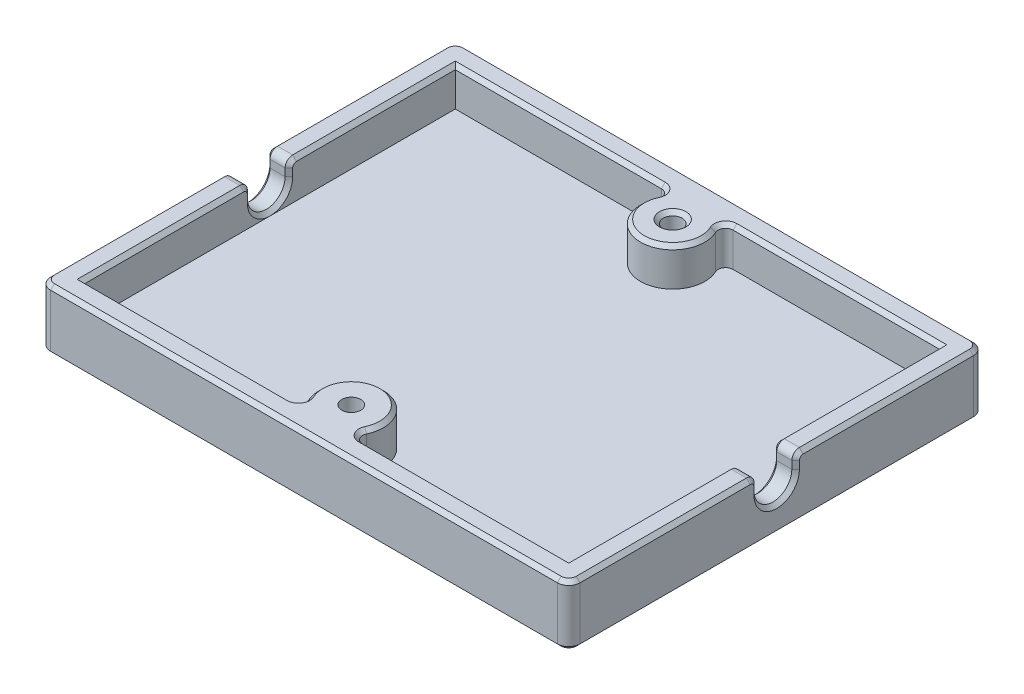
SolidWorks part; units mm, degrees
ref_plane "Front Plane" through (0, 0, 0) normal (0, 0, 1) x (1, 0, 0)
ref_plane "Top Plane" through (0, 0, 0) normal (0, 1, 0) x (1, 0, 0)
ref_plane "Right Plane" through (0, 0, 0) normal (1, 0, 0) x (0, 0, -1)
sketch "Sketch1" plane through (0, 0, 0) normal (0, 1, 0) x (1, 0, 0)
  line L1 (-70, -55) -> (70, -55)
  line L2 (-70, -55) -> (-70, 55)
  line L3 (-70, 55) -> (70, 55)
  line L4 (70, -55) -> (70, 55)
  line L5 (-70, -55) -> (70, 55) construction
  line L6 (-70, 55) -> (70, -55) construction
  point P0 (0, 0)
  dimension "D1" = 140
  dimension "D2" = 110
extrude "Boss-Extrude1" add sketch "Sketch1" along normal blind 16
sketch "Sketch2" plane through (0, 16, 0) normal (0, 1, 0) x (1, 0, 0)
  line L0 (0, 42.5) -> (0, 0) construction
  line L1 (-70, 0) -> (70, 0) construction
  line L2 (-70, 55) -> (-70, -55) construction
  line L3 (70, -55) -> (70, 55) construction
  circle A0 centre (0, 42.5) radius 2.5
  circle A1 centre (0, -42.5) radius 2.5
  dimension "D2" = 5
  dimension "D1" = 85
extrude "Cut-Extrude1" cut sketch "Sketch2" against normal through all
fillet "Fillet1" radius 3 4 edges at (-70, 8, -55) (70, 8, -55) (-70, 8, 55) (70, 8, 55)
shell "Shell1" thickness 6 removed face at (0, 16, -40)
sketch "Sketch3" plane through (70, 0, 0) normal (1, 0, 0) x (0, 0, -1)
  line L0 (0, 20) -> (0, 12) construction
  line L1 (-52, 16) -> (52, 16) construction
  line L2 (5, 20) -> (5, 12)
  line L3 (-5, 20) -> (-5, 12)
  arc A0 (5, 20) -> (-5, 20) centre (0, 20) ccw
  arc A1 (-5, 12) -> (5, 12) centre (0, 12) ccw
  point P5 (0, 16)
  point P10 (0, 7)
  dimension "D1" = 10
  dimension "D2" = 9
extrude "Cut-Extrude2" cut sketch "Sketch3" against normal through all
fillet "Fillet2" radius 2 8 edges at (67, 16, 5) (67, 16, -5) (-67, 16, -5) (-67, 16, 5) (-5.4772, 11, 49) (5.4772, 11, 49) (5.4772, 11, -49) (-5.4772, 11, -49)
chamfer "Chamfer2" distance 1 angle 45 55 edges at (0, 16, 55) (-69.1213, 16, 54.1213) (69.1213, 16, 54.1213) (-70, 16, 29.5) (70, 16, 29.5) (-70, 15.4142, 5.5858) (70, 15.4142, 5.5858) (-70, 13, 5) (70, 13, 5) (-70, 7, 0) (70, 7, 0) (-70, 13, -5) (70, 13, -5) (-70, 15.4142, -5.5858) (70, 15.4142, -5.5858) (-70, 16, -29.5) (-69.1213, 16, -54.1213) (0, 16, -55) (69.1213, 16, -54.1213) (70, 16, -29.5) (-64, 16, 28) (64, 16, 28) (-64, 15.4142, 5.5858) (64, 15.4142, 5.5858) (-64, 13, 5) (64, 13, 5) (-64, 7, 0) (64, 7, 0) (-64, 13, -5) (64, 13, -5) (-64, 15.4142, -5.5858) (64, 15.4142, -5.5858) (-64, 16, -28) (-36.7434, 16, -49) (-7.7965, 16, -48.069) (0, 16, -34) (7.7965, 16, -48.069) (36.7434, 16, -49) (64, 16, -28) (0, 16, -40) (-69.1213, 0, 54.1213) (0, 0, 55) (69.1213, 0, 54.1213) (70, 0, 0) (69.1213, 0, -54.1213) (0, 0, -55) (-69.1213, 0, -54.1213) (-70, 0, 0) (0, 0, 40) (0, 0, -40) (36.7434, 16, 49) (7.7965, 16, 48.069) (0, 16, 34) (-36.7434, 16, 49) (-7.7965, 16, 48.069)
